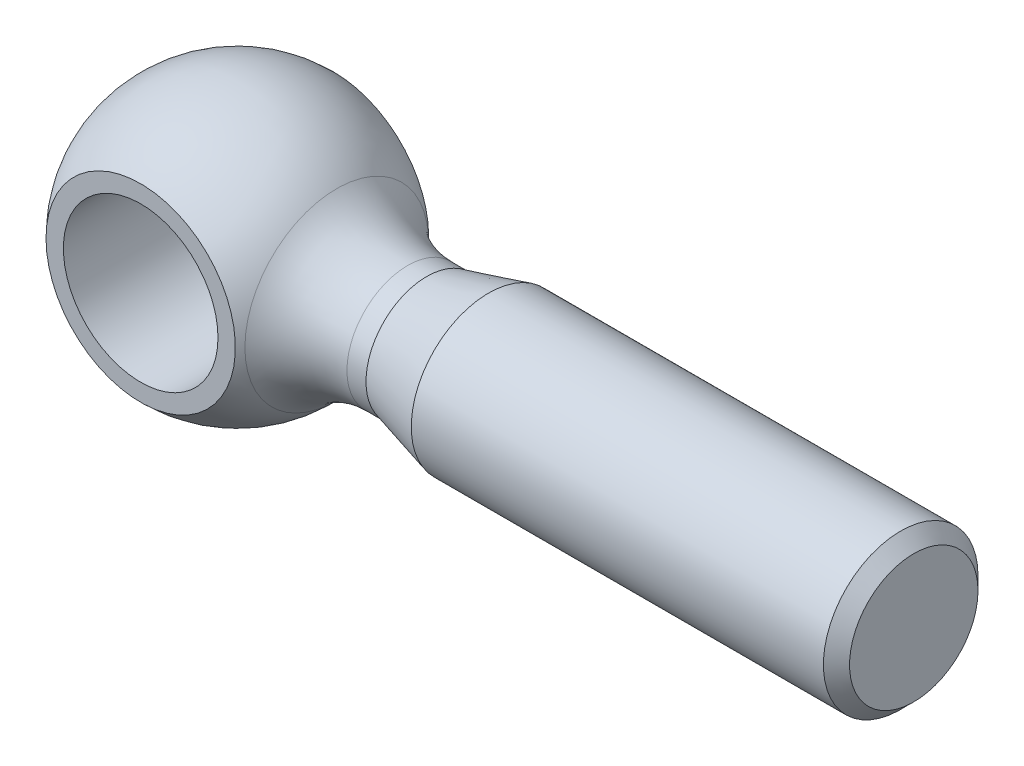
SolidWorks part; units mm, degrees
ref_plane "Front" through (0, 0, 0) normal (0, 0, 1) x (1, 0, 0)
ref_plane "Top" through (0, 0, 0) normal (0, 1, 0) x (1, 0, 0)
ref_plane "Right" through (0, 0, 0) normal (1, 0, 0) x (0, 0, -1)
sketch "Sketch2" plane through (0, 0, 0) normal (1, 0, 0) x (0, 0, -1)
  circle A0 centre (0, 0) radius 4
extrude "BaseBody" add sketch "Sketch2" along normal blind 35 separate body
cosmetic thread "ThreadCosmetic1" [suppressed] parameters "b"=22, "D2"=6.647
sketch "Sketch5" plane through (0, 0, 0) normal (0, 0, 1) x (1, 0, 0)
  line L0 (0, 3.1426) -> (9.8, 3.1426)
  line L1 (9.8, 3.1426) -> (13, 4)
  line L2 (35, 4) -> (0, 4) construction
  line L3 (13, 4) -> (0, 4)
  line L4 (0, 4) -> (0, 3.1426)
  line L5 (0, 4) -> (0, -4) construction
  dimension "D1" = 15
  dimension "D3" = 13
revolve "Cut-Revolve1" cut sketch "Sketch5" angle 360 about axis through (35, 0, 0) along (-1, 0, 0)
sketch "Sketch1" plane through (0.9567, 0, -6.0433) normal (0, 1, 0) x (0, 0, -1)
  line L0 (-13.0433, 0.9567) -> (0.9567, 0.9567)
  line L1 (-19.3915, 0.9567) -> (2.2184, 0.9567) construction
  arc A0 (0.9567, 0.9567) -> (-13.0433, 0.9567) centre (-6.0433, 0.9567) ccw
  dimension "SD" = 14
revolve "BaseHead" add sketch "Sketch1" angle 360 about L1
sketch "Sketch3" plane through (0, 0, 0) normal (1, 0, 0) x (0, 0, -1)
  line L0 (-5, 4.899) -> (-5, -4.899)
  line L1 (5, 4.899) -> (5, -4.899)
  arc A1 (-5, 4.899) -> (-5, -4.899) centre (0, 0) ccw
  arc A2 (5, -4.899) -> (5, 4.899) centre (0, 0) ccw
  dimension "D2" = 5
extrude "Cut-Extrude1" cut sketch "Sketch3" against normal through all and the other way through all
sketch "Sketch4" plane through (0, 0, 5) normal (0, 0, 1) x (1, 0, 0)
  circle A0 centre (0, 0) radius 4
  dimension "d1" = 8
extrude "Hole" cut sketch "Sketch4" against normal through all
chamfer "Chamfer1" distance 0.6765 angle 45 1 edges at (35, 0, -4)
fillet "HeadFillet" radius 5 1 edges at (6.2549, 0, 3.1426)
sketch "Sketch6" plane through (0, 0, 0) normal (0, 0, 1) x (1, 0, 0)
  line L0 (33.647, 4.6765) -> (34.3235, 4.6765)
  line L1 (34.3235, 4.6765) -> (34.3235, 4)
  line L2 (34.3235, 4) -> (33.9853, 3.4141)
  line L3 (33.9853, 3.4141) -> (33.647, 4)
  line L4 (33.647, 4) -> (33.647, 4.6765)
  line L5 (34.3235, -4) -> (34.3235, 4) construction
  line L6 (34.3235, 4) -> (13, 4) construction
  dimension "D1" = 0.6765
revolve "Cut-Revolve10" [suppressed] cut sketch "Sketch6" angle 360
pattern_linear "LPattern10" [suppressed] count 27 of bodies 107
equation "\"D2@Sketch3\" = \"s@Sketch3\" / 2"
equation "\"C1@Chamfer1\" =  (\"d@Sketch2\" - \"D2@ThreadCosmetic1\" )  / 2"
equation "\"D3@Sketch5\" = \"l@BaseBody\" - \"b@ThreadCosmetic1\""
equation "\"D1@Sketch6\" =  ( \"d@Sketch2\" - \"D2@ThreadCosmetic1\" )  / 2"
equation "\"pitch@LPattern10\" = 1.2 * \"D1@Sketch6\""
equation "\"D1@LPattern10\" = \"b@ThreadCosmetic1\" / \"pitch@LPattern10\""
